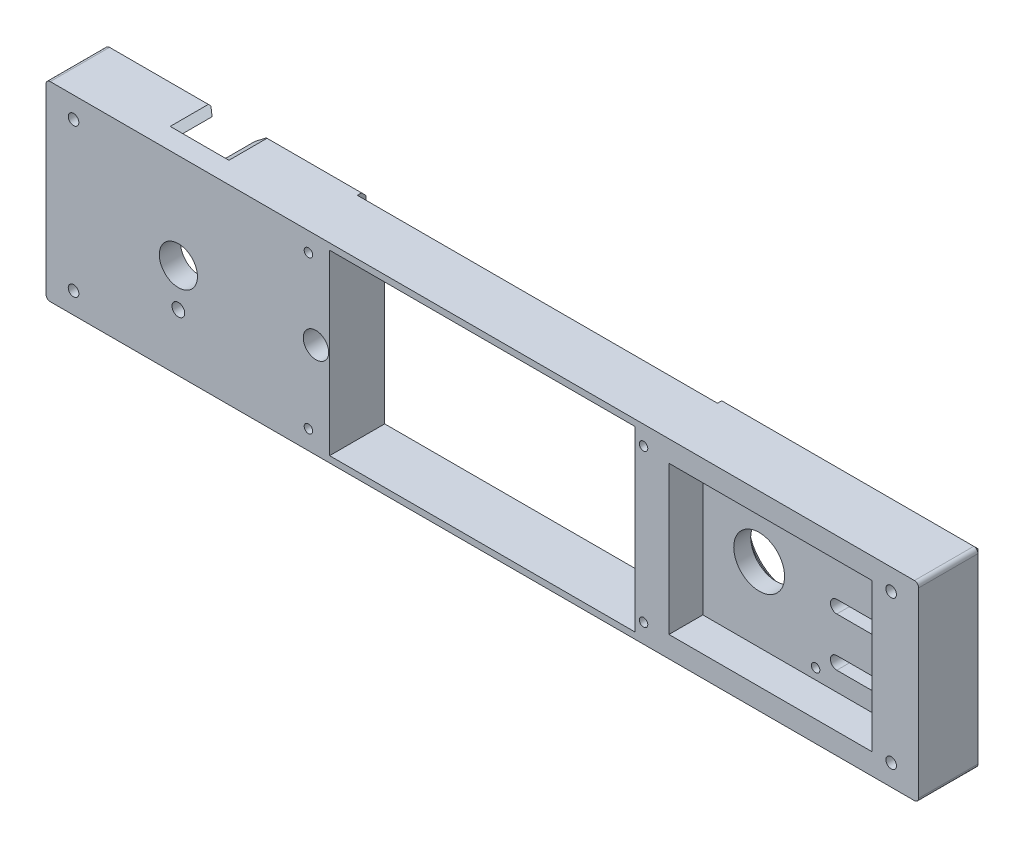
SolidWorks part; units mm, degrees
ref_plane "Front" through (0, 0, 0) normal (0, 0, 1) x (1, 0, 0)
ref_plane "Top" through (0, 0, 0) normal (0, 1, 0) x (1, 0, 0)
ref_plane "Right" through (0, 0, 0) normal (1, 0, 0) x (0, 0, -1)
sketch "草图1" plane through (0, 0, 0) normal (0, 0, 1) x (1, 0, 0)
  line L0 (0, 45) -> (206, 0) construction
  line L1 (0, 0) -> (206, 0)
  line L2 (0, 0) -> (0, 45)
  line L3 (0, 45) -> (206, 45)
  line L4 (206, 0) -> (206, 45)
  line L5 (206, 45) -> (0, 0) construction
  line L6 (66.95, 22.5) -> (60.5, 22.5) construction
  line L7 (60.5, 0) -> (145.5, 0)
  line L8 (60.5, 0) -> (60.5, 45)
  line L9 (60.5, 45) -> (145.5, 45)
  line L10 (145.5, 0) -> (145.5, 45)
  line L11 (60.5, 0) -> (145.5, 45) construction
  line L12 (60.5, 45) -> (145.5, 0) construction
  line L13 (66.95, 1.5) -> (139.05, 1.5)
  line L14 (66.95, 1.5) -> (66.95, 43.5)
  line L15 (66.95, 43.5) -> (139.05, 43.5)
  line L16 (139.05, 1.5) -> (139.05, 43.5)
  line L17 (66.95, 1.5) -> (139.05, 43.5) construction
  line L18 (66.95, 43.5) -> (139.05, 1.5) construction
  line L19 (60.725, 25.5) -> (66.725, 25.5)
  line L20 (60.725, 25.5) -> (60.725, 19.5)
  line L21 (60.725, 19.5) -> (66.725, 19.5)
  line L22 (66.725, 25.5) -> (66.725, 19.5)
  line L23 (60.725, 25.5) -> (66.725, 19.5) construction
  line L24 (60.725, 19.5) -> (66.725, 25.5) construction
  circle A0 centre (63.725, 22.5) radius 3
  point P5 (103, 22.5)
  point P11 (63.725, 22.5)
  point P17 (103, 22.5)
  dimension "D5" = 6
  dimension "D1" = 206
  dimension "D2" = 45
  dimension "D3" = 85
  dimension "D4" = 45
  dimension "D6" = 72.1
  dimension "D7" = 42
  dimension "D8" = 6
extrude "凸台-拉伸1" add sketch "草图1" along normal blind 15 contours L1 L4 L3 L2
extrude "切除-拉伸1" cut sketch "草图1<4>" along normal blind 2 contours L8 L9 L10 L7
sketch "草图1<4>" plane through (0, 0, 0) normal (0, 0, 1) x (1, 0, 0) same geometry as "草图1"
extrude "切除-拉伸2" cut sketch "草图1<5>" along normal blind 71 contours L16 L15 L14 L13
sketch "草图1<5>" plane through (0, 0, 0) normal (0, 0, 1) x (1, 0, 0) same geometry as "草图1"
extrude "切除-拉伸3" cut sketch "草图1<6>" along normal blind 42 contours A0 region at (63.725, 22.5, 0)
sketch "草图1<6>" plane through (0, 0, 0) normal (0, 0, 1) x (1, 0, 0) same geometry as "草图1"
sketch "草图2" plane through (0, 0, 0) normal (0, 0, -1) x (-1, 0, 0)
  line L0 (-31.25, 22.5) -> (-31.25, 44.5)
  line L3 (-31.25, 45) -> (-31.25, 0) construction
  circle A0 centre (-31.25, 22.5) radius 22
  circle A1 centre (-31.25, 22.5) radius 4.5
  dimension "D1" = 44
  dimension "D3" = 9
extrude "切除-拉伸4" cut sketch "草图2" against normal blind 10 contours A0 L0 | L0 A0 region at (16.1337, 37.6163, 0)
extrude "切除-拉伸5" cut sketch "草图2<3>" against normal blind 50 contours A1 L0 | L0 A1 region at (28.158, 25.592, 0)
sketch "草图2<3>" plane through (0, 0, 0) normal (0, 0, -1) x (-1, 0, 0) same geometry as "草图2"
sketch "草图3" plane through (0, 0, 0) normal (0, 0, -1) x (-1, 0, 0)
  line L0 (-139.05, 43.5) -> (-66.95, 1.5) construction
  line L1 (-203, 2) -> (-3, 2)
  line L2 (-203, 2) -> (-203, 43)
  line L3 (-203, 43) -> (-3, 43)
  line L4 (-3, 2) -> (-3, 43)
  line L5 (-203, 2) -> (-3, 43) construction
  line L6 (-203, 43) -> (-3, 2) construction
  line L7 (-139.05, 1.5) -> (-66.95, 43.5) construction
  line L8 (-15.5, 43) -> (-15.5, 2)
  point P0 (-103, 22.5)
  point P15 (-3, 22.5)
  dimension "D1" = 200
  dimension "D2" = 41
  dimension "D3" = 12.5
sketch "草图4" plane through (0, 0, 15) normal (0, 0, 1) x (1, 0, 0)
  line L0 (31.25, 13.5) -> (31.25, 22.5)
  line L1 (31.25, 22.5) -> (31.25, 13.5)
  circle A0 centre (31.25, 22.5) radius 9
  circle A1 centre (31.25, 13.5) radius 1.5
  dimension "D1" = 18
  dimension "D3" = 3
  dimension "D2" = 0
extrude "切除-拉伸6" cut sketch "草图4" against normal blind 44 and the other way blind 17 contours A1
sketch "草图5" plane through (0, 0, 0) normal (0, 0, -1) x (-1, 0, 0)
  line L0 (-186.6654, 34) -> (-178.6654, 34) construction
  line L1 (-186.6654, 35.5) -> (-178.6654, 35.5)
  line L2 (-186.6654, 32.5) -> (-178.6654, 32.5)
  line L3 (-186.6654, 11) -> (-178.6654, 11) construction
  line L4 (-186.6654, 12.5) -> (-178.6654, 12.5)
  line L5 (-186.6654, 9.5) -> (-178.6654, 9.5)
  line L6 (-182.6654, 45) -> (-182.6654, 0) construction
  line L7 (-145.5, 45) -> (-206, 45) construction
  line L8 (-145.5, 0) -> (-206, 0) construction
  line L9 (-186.6654, 22.5) -> (-178.6654, 22.5) construction
  line L10 (-186.6654, 24) -> (-178.6654, 24)
  line L11 (-186.6654, 21) -> (-178.6654, 21)
  arc A0 (-186.6654, 35.5) -> (-186.6654, 32.5) centre (-186.6654, 34) ccw
  arc A1 (-178.6654, 32.5) -> (-178.6654, 35.5) centre (-178.6654, 34) ccw
  arc A2 (-186.6654, 12.5) -> (-186.6654, 9.5) centre (-186.6654, 11) ccw
  arc A3 (-178.6654, 9.5) -> (-178.6654, 12.5) centre (-178.6654, 11) ccw
  arc A4 (-186.6654, 24) -> (-186.6654, 21) centre (-186.6654, 22.5) ccw
  arc A5 (-178.6654, 21) -> (-178.6654, 24) centre (-178.6654, 22.5) ccw
  point P2 (-182.6654, 34)
  point P9 (-182.6654, 11)
  point P14 (-182.6654, 34)
  point P15 (-182.6654, 11)
  point P22 (-182.6654, 22.5)
  point P27 (-182.6654, 22.5)
  point P32 (-189.0753, 23.5128)
  dimension "D2" = 1.5
  dimension "D8" = 1.5
  dimension "D9" = 1.5
  dimension "D1" = 8
  dimension "D3" = 8
  dimension "D4" = 11.5
  dimension "D5" = 45
  dimension "D6" = 11.5
  dimension "D7" = 8
extrude "切除-拉伸7" cut sketch "草图5" against normal blind 14
chamfer "倒角1" distance 1 angle 45 12 edges at (177.1654, 34, 0) (182.6654, 35.5, 0) (188.1654, 34, 0) (182.6654, 32.5, 0) (188.1654, 11, 0) (182.6654, 9.5, 0) (182.6654, 12.5, 0) (177.1654, 11, 0) (188.1654, 22.5, 0) (182.6654, 21, 0) (182.6654, 24, 0) (177.1654, 22.5, 0)
chamfer "倒角2" distance 2 angle 45 1 edges at (9.25, 22.5, 0)
sketch "草图6" plane through (0, 0, 0) normal (0, 0, -1) x (-1, 0, 0)
  line L0 (-31.25, 23) -> (-31.25, -16.3208)
  line L1 (-31.25, -16.3208) -> (-31.25, 54.112)
  line L2 (-31.25, 41) -> (-53.9606, 54.112)
  line L3 (-53.9606, 54.112) -> (-8.5394, 54.112)
  line L4 (-8.5394, 54.112) -> (-31.25, 41)
  line L5 (-31.25, 5) -> (-68.1787, -16.3208)
  line L6 (-68.1787, -16.3208) -> (5.6787, -16.3208)
  line L7 (5.6787, -16.3208) -> (-31.25, 5)
  point P3 (-31.25, 5)
  point P5 (-31.25, 41)
  line M5 (0, 45) -> (-22.8984, 45)
  arc M6 (-22.8984, 45) -> (-22.8984, 0) centre (-31.25, 22.5) cw
  line M7 (-22.8984, 0) -> (0, 0)
  dimension "D1" = 18
  dimension "D2" = 18
  dimension "D3" = 60
  dimension "D4" = 60
  dimension "D5" = 60
  dimension "D6" = 60
extrude "切除-拉伸9" cut sketch "草图6" against normal up to surface (10 mm away) contours L6 L7 L1 M7 M6 | L5 L6 L1 | L4 L3 L1 M6 M5 | L3 L2 L1 region at (18.9403, -9.2141, 0) region at (43.5596, -9.2139, 0) region at (38.8202, 49.7413, 0) region at (23.6798, 49.7413, 0) up to face at (29.75, 13.5, 10)
sketch "草图7" plane through (0, 0, 0) normal (0, 0, -1) x (-1, 0, 0)
  line L0 (-145.5, 22.5) -> (-203, 22.5) construction
  line L3 (-145.5, 0) -> (-145.5, 45) construction
  line L4 (-203, 2) -> (-203, 43) construction
  circle A0 centre (-160.3418, 22.5) radius 6
  circle A1 centre (-160.3418, 22.5) radius 8.5
  dimension "D3" = 12
  dimension "D4" = 17
extrude "切除-拉伸10" cut sketch "草图7" against normal blind 182 contours A0 | L0 A0 region at (160.3418, 19.9535, 0) region at (160.3418, 25.0465, 0)
extrude "切除-拉伸11" cut sketch "草图7<4>" against normal blind 3 contours A1 A0 | L0 A1 A0 region at (160.3418, 14.1901, 0) region at (153.0918, 22.6901, 0)
sketch "草图7<4>" plane through (0, 0, 0) normal (0, 0, -1) x (-1, 0, 0) same geometry as "草图7"
chamfer "倒角3" distance 1 angle 45 1 edges at (151.8418, 22.5, 0)
sketch "草图9" plane through (0, 0, 0) normal (0, 0, -1) x (-1, 0, 0)
  line L0 (-206, 0) -> (-206, 45) construction
  line L1 (-6.5, 5) -> (-199.5, 5)
  line L2 (-6.5, 5) -> (-6.5, 40)
  line L3 (-6.5, 40) -> (-199.5, 40)
  line L4 (-199.5, 5) -> (-199.5, 40)
  line L5 (-6.5, 5) -> (-199.5, 40) construction
  line L6 (-6.5, 40) -> (-199.5, 5) construction
  line L7 (-145.5, 0) -> (-206, 0) construction
  circle A0 centre (-199.5, 40) radius 1.25
  circle A1 centre (-199.5, 40) radius 2.5
  circle A2 centre (-199.5, 5) radius 1.25
  circle A3 centre (-199.5, 5) radius 2.5
  circle A4 centre (-6.5, 5) radius 1.25
  circle A5 centre (-6.5, 5) radius 2.5
  circle A6 centre (-6.5, 40) radius 1.25
  circle A7 centre (-6.5, 40) radius 2.5
  point P0 (-103, 22.5)
  dimension "D3" = 2.5
  dimension "D4" = 5
  dimension "D1" = 6.5
  dimension "D2" = 5
extrude "切除-拉伸12" cut sketch "草图9" against normal blind 182 contours A6 | A4 | A2 | A0
extrude "切除-拉伸13" cut sketch "草图9<3>" against normal blind 3 contours A1 | A3 | A5 | A7
sketch "草图9<3>" plane through (0, 0, 0) normal (0, 0, -1) x (-1, 0, 0) same geometry as "草图9"
fillet "圆角1" radius 1 4 edges at (206, 0, 7.5) (206, 45, 7.5) (0, 0, 7.5) (0, 45, 7.5)
sketch "草图10" plane through (0, 0, 15) normal (0, 0, 1) x (1, 0, 0)
  line L0 (203, 43) -> (3, 43) construction
  line L1 (147.05, 40) -> (195, 40)
  line L2 (147.05, 40) -> (147.05, 5)
  line L3 (147.05, 5) -> (195, 5)
  line L4 (195, 40) -> (195, 5)
  line L5 (203, 2) -> (3, 2) construction
  line L6 (203, 2) -> (203, 43) construction
  line L7 (139.05, 1.5) -> (139.05, 43.5) construction
  dimension "D1" = 3
  dimension "D2" = 3
  dimension "D3" = 8
  dimension "D4" = 8
extrude "切除-拉伸14" cut sketch "草图10" against normal blind 8
sketch "草图11" plane through (0, 0, 7) normal (0, 0, 1) x (1, 0, 0)
  line L1 (170.77, 40) -> (170.77, 5)
  line L2 (186.6654, 21) -> (178.6654, 21) construction
  line L3 (195, 40) -> (147.05, 40) construction
  line L4 (182.6654, 40) -> (182.6654, 5)
  line L8 (147.05, 5) -> (195, 5) construction
  line L9 (182.6654, 21) -> (182.6654, 24)
  line L10 (178.6654, 24) -> (186.6654, 24) construction
  line L11 (173.6654, 7.5) -> (191.6654, 7.5)
  line L12 (173.6654, 7.5) -> (173.6654, 37.5)
  line L13 (173.6654, 37.5) -> (191.6654, 37.5)
  line L14 (191.6654, 7.5) -> (191.6654, 37.5)
  line L15 (173.6654, 7.5) -> (191.6654, 37.5) construction
  line L16 (173.6654, 37.5) -> (191.6654, 7.5) construction
  line L17 (195, 5) -> (195, 40) construction
  circle A0 centre (191.6654, 37.5) radius 1
  circle A1 centre (173.6654, 37.5) radius 1
  circle A2 centre (173.6654, 7.5) radius 1
  circle A3 centre (191.6654, 7.5) radius 1
  point P9 (182.6654, 22.5)
  point P15 (182.6654, 22.5)
  point P26 (170.77, 22.5)
  dimension "D7" = 24.23
  dimension "D8" = 2.5
  dimension "D9" = 2.5
  dimension "D10" = 2.8954
  dimension "D3" = 2
  dimension "D4" = 2
  dimension "D5" = 2
  dimension "D6" = 2
  dimension "D1" = 18
  dimension "D2" = 30
  dimension "D11" = 3.3346
extrude "切除-拉伸15" cut sketch "草图11" against normal blind 3 contours A1 | A2 | A3 | A0
chamfer "倒角4" distance 1 angle 45 12 edges at (175.25, 0, 0) (205.7071, 0.2929, 0) (206, 22.5, 0) (205.7071, 44.7071, 0) (175.25, 45, 0) (50.2051, 0, 0) (50.0508, 45, 0) (11.9492, 0, 0) (11.9492, 45, 0) (0.2929, 0.2929, 0) (0.2929, 44.7071, 0) (0, 22.5, 0)
sketch "草图12" plane through (0, 0, 15) normal (0, 0, 1) x (1, 0, 0)
  line L1 (64.9661, 4.5) -> (141.05, 4.5)
  line L2 (64.9661, 4.5) -> (64.9661, 40.5)
  line L3 (64.9661, 40.5) -> (141.05, 40.5)
  line L4 (141.05, 4.5) -> (141.05, 40.5)
  line L5 (64.9661, 4.5) -> (141.05, 40.5) construction
  line L6 (64.9661, 40.5) -> (141.05, 4.5) construction
  line L7 (64.9661, 40.5) -> (61.95, 40.5)
  line L8 (64.9661, 40.5) -> (64.9661, 4.5)
  line L9 (64.9661, 4.5) -> (61.95, 4.5)
  line L11 (139.05, 1.5) -> (139.05, 43.5) construction
  line L12 (147.05, 40) -> (147.05, 5) construction
  line L13 (1, 45) -> (205, 45) construction
  line L14 (1, 0) -> (205, 0) construction
  circle A0 centre (61.95, 40.5) radius 1
  circle A1 centre (61.95, 4.5) radius 1
  circle A2 centre (141.05, 4.5) radius 1
  circle A3 centre (141.05, 40.5) radius 1
  point P0 (103.0081, 22.5)
  dimension "D1" = 2
  dimension "D2" = 2
  dimension "D3" = 2
  dimension "D4" = 2
  dimension "D6" = 2
  dimension "D7" = 6
  dimension "D8" = 4.5
  dimension "D9" = 4.5
  dimension "D11" = 36
extrude "切除-拉伸16" cut sketch "草图12" against normal blind 5 contours A0 | A1 | A2 | A3
